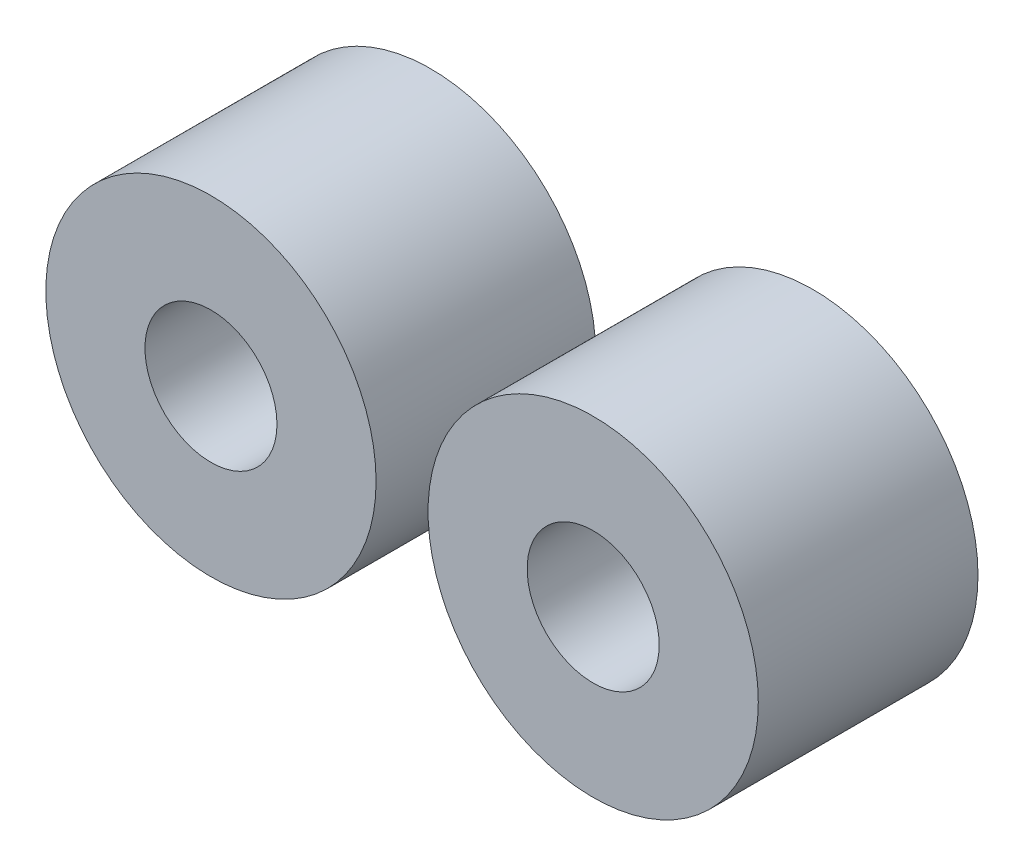
SolidWorks part; units mm, degrees
ref_plane "Płaszczyzna przednia" through (0, 0, 0) normal (0, 0, 1) x (1, 0, 0)
ref_plane "Płaszczyzna górna" through (0, 0, 0) normal (0, 1, 0) x (1, 0, 0)
ref_plane "Płaszczyzna prawa" through (0, 0, 0) normal (1, 0, 0) x (0, 0, -1)
sketch "Szkic1" plane through (0, 0, 0) normal (0, 0, 1) x (1, 0, 0)
  line L0 (0, 0) -> (2206, 0) construction
  circle A0 centre (0, 0) radius 381
  circle A1 centre (0, 0) radius 953
  circle A2 centre (2206, 0) radius 953
  circle A3 centre (2206, 0) radius 381
  dimension "D1" = 762
  dimension "D2" = 1906
  dimension "D4" = 2206
  dimension "D3" = 2
extrude "Dodanie-wyciągnięcie1" add sketch "Szkic1" along normal blind 1268
ref_axis "Oś1" through (0, 0, 1268) along (0, 0, -1)
ref_axis "Oś2" through (2206, 0, 1268) along (0, 0, -1)
